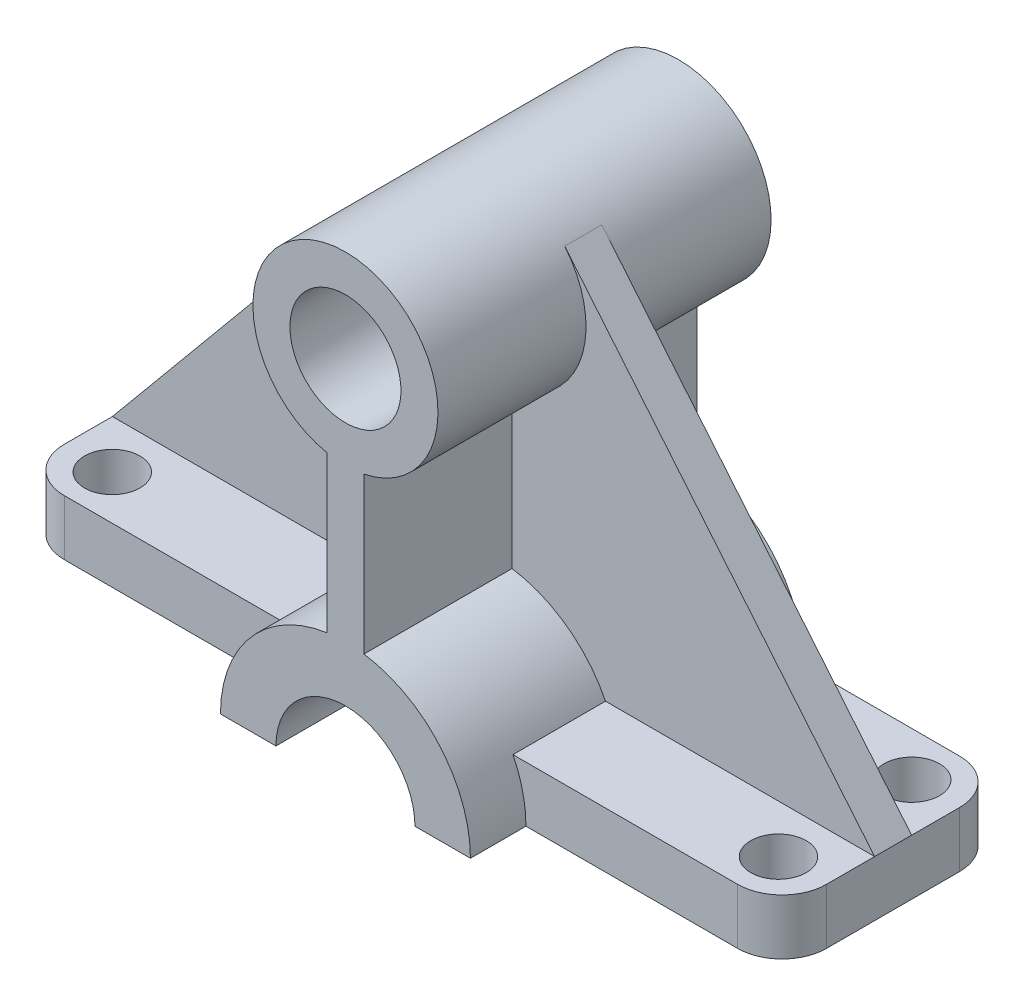
SolidWorks part; units mm, degrees
ref_plane "Front Plane" through (0, 0, 0) normal (0, 0, 1) x (1, 0, 0)
ref_plane "Top Plane" through (0, 0, 0) normal (0, 1, 0) x (1, 0, 0)
ref_plane "Right Plane" through (0, 0, 0) normal (1, 0, 0) x (0, 0, -1)
sketch "Sketch1" plane through (0, 0, 0) normal (0, 0, 1) x (1, 0, 0)
  line L0 (-33.7725, 0) -> (-18.7814, 0)
  line L3 (5, 33.4004) -> (5, 75.5051)
  line L4 (-5, 33.4004) -> (-5, 75.5051)
  line L7 (18.7814, 0) -> (33.7725, 0)
  arc A0 (33.7725, 0) -> (5, 33.4004) centre (0, 0) ccw
  arc A1 (18.7814, 0) -> (-18.7814, 0) centre (0, 0) ccw
  arc A2 (5, 75.5051) -> (-5, 75.5051) centre (0, 100) ccw
  circle A3 centre (0, 100) radius 15
  arc A4 (0, 33.7725) -> (-33.7725, 0) centre (0, 0) ccw
  point P4 (0, 0)
  dimension "D6" = 50
  dimension "D7" = 30
  dimension "D5" = 100
extrude "Boss-Extrude1" add sketch "Sketch1" along normal mid plane 90 contours L4 A4 L0 A1 L7 A0 L3 A2 A3 region at (0, 58.266, 0)
sketch "Sketch4" plane through (0, 0, 0) normal (0, 1, 0) x (1, 0, 0)
  line L1 (-90.9628, -30) -> (90.9628, -30)
  line L2 (-90.9628, 30) -> (90.9628, 30)
  line L3 (-102.9628, 18) -> (-102.9628, -18)
  line L4 (102.9628, 18) -> (102.9628, -18)
  line L7 (0, 30) -> (0, -30) construction
  arc A0 (90.9628, 30) -> (102.9628, 18) centre (90.9628, 18) cw
  arc A1 (90.9628, -30) -> (102.9628, -18) centre (90.9628, -18) ccw
  arc A2 (-90.9628, -30) -> (-102.9628, -18) centre (-90.9628, -18) cw
  arc A3 (-90.9628, 30) -> (-102.9628, 18) centre (-90.9628, 18) ccw
  circle A4 centre (-90, 18) radius 7.5
  circle A5 centre (90, 18) radius 7.5
  circle A6 centre (90, -18) radius 7.5
  circle A7 centre (-90, -18) radius 7.5
  point P4 (0, 0)
  point P24 (0, 0)
  dimension "D3" = 12
  dimension "D8" = 15
extrude "Boss-Extrude2" add sketch "Sketch4" along normal blind 15
sketch "Sketch5" plane through (0, 0, 30) normal (0, 0, 1) x (1, 0, 0)
  line L2 (-18.7814, 0) -> (18.7814, 0)
  line L3 (11.3023, 15) -> (-11.3023, 15)
  line L4 (-18.7814, 0) -> (18.7814, 0)
  line L5 (11.3023, 15) -> (-11.3023, 15)
  arc A2 (-11.3023, 15) -> (-18.7814, 0) centre (0, 0) ccw
  arc A3 (18.7814, 0) -> (11.3023, 15) centre (0, 0) ccw
  arc A4 (-11.3023, 15) -> (-18.7814, 0) centre (0, 0) ccw
  arc A5 (18.7814, 0) -> (11.3023, 15) centre (0, 0) ccw
  dimension "D1" = 0
extrude "Cut-Extrude1" cut sketch "Sketch5" against normal through all
sketch "Sketch6" plane through (0, 0, 0) normal (0, 0, 1) x (1, 0, 0)
  line L0 (-19.2442, 115.9581) -> (-102.9628, 15)
  line L1 (19.2442, 115.9581) -> (102.9628, 15)
  line L2 (90.9628, 0) -> (102.9628, 0) construction
  line L3 (102.9628, 0) -> (102.9628, 15) construction
  line L4 (102.9628, 15) -> (90.9628, 15) construction
  line L5 (90.9628, 15) -> (30.2586, 15) construction
  line L6 (-5, 75.5051) -> (-5, 33.4004)
  line L7 (-33.7725, 0) -> (-18.7814, 0)
  line L8 (18.7814, 0) -> (33.7725, 0)
  line L9 (5, 33.4004) -> (5, 75.5051)
  line L10 (-5, 75.5051) -> (-5, 33.4004)
  line L11 (-33.7725, 0) -> (-18.7814, 0)
  line L12 (18.7814, 0) -> (33.7725, 0)
  line L13 (5, 33.4004) -> (5, 75.5051)
  line L14 (33.7725, 0) -> (90.9628, 0) construction
  line L15 (-102.9628, 0) -> (-90.9628, 0) construction
  line L16 (-90.9628, 15) -> (-102.9628, 15) construction
  line L17 (-102.9628, 15) -> (-102.9628, 0) construction
  line L18 (-90.9628, 0) -> (-33.7725, 0) construction
  line L19 (-30.2586, 15) -> (-90.9628, 15) construction
  line L20 (90.9628, 0) -> (102.9628, 0)
  line L21 (102.9628, 0) -> (102.9628, 15)
  line L22 (102.9628, 15) -> (90.9628, 15)
  line L23 (90.9628, 15) -> (30.2586, 15)
  line L24 (33.7725, 0) -> (90.9628, 0)
  line L25 (-102.9628, 0) -> (-90.9628, 0)
  line L26 (-90.9628, 15) -> (-102.9628, 15)
  line L27 (-102.9628, 15) -> (-102.9628, 0)
  line L28 (-90.9628, 0) -> (-33.7725, 0)
  line L29 (-30.2586, 15) -> (-90.9628, 15)
  arc A0 (5, 75.5051) -> (-5, 75.5051) centre (0, 100) ccw construction
  arc A1 (33.7725, 0) -> (30.2586, 15) centre (0, 0) ccw construction
  arc A2 (-30.2586, 15) -> (-33.7725, 0) centre (0, 0) ccw construction
  arc A3 (33.7725, 0) -> (30.2586, 15) centre (0, 0) ccw
  arc A4 (-30.2586, 15) -> (-33.7725, 0) centre (0, 0) ccw
  arc A5 (-5, 33.4004) -> (-33.7725, 0) centre (0, 0) ccw
  arc A6 (18.7814, 0) -> (-18.7814, 0) centre (0, 0) ccw
  arc A7 (33.7725, 0) -> (5, 33.4004) centre (0, 0) ccw
  arc A8 (5, 75.5051) -> (-5, 75.5051) centre (0, 100) ccw
  arc A9 (-5, 33.4004) -> (-33.7725, 0) centre (0, 0) ccw
  arc A10 (18.7814, 0) -> (-18.7814, 0) centre (0, 0) ccw
  arc A11 (33.7725, 0) -> (5, 33.4004) centre (0, 0) ccw
  arc A12 (5, 75.5051) -> (-5, 75.5051) centre (0, 100) ccw
  dimension "D1" = 0
extrude "Boss-Extrude3" add sketch "Sketch6" along normal mid plane 10 contours A12 L13 A11 L23 L22 L1 | A12 L0 L26 L29 A9 L10 region at (-43.2598, 48.6978, 0) region at (43.2598, 48.6978, 0)
